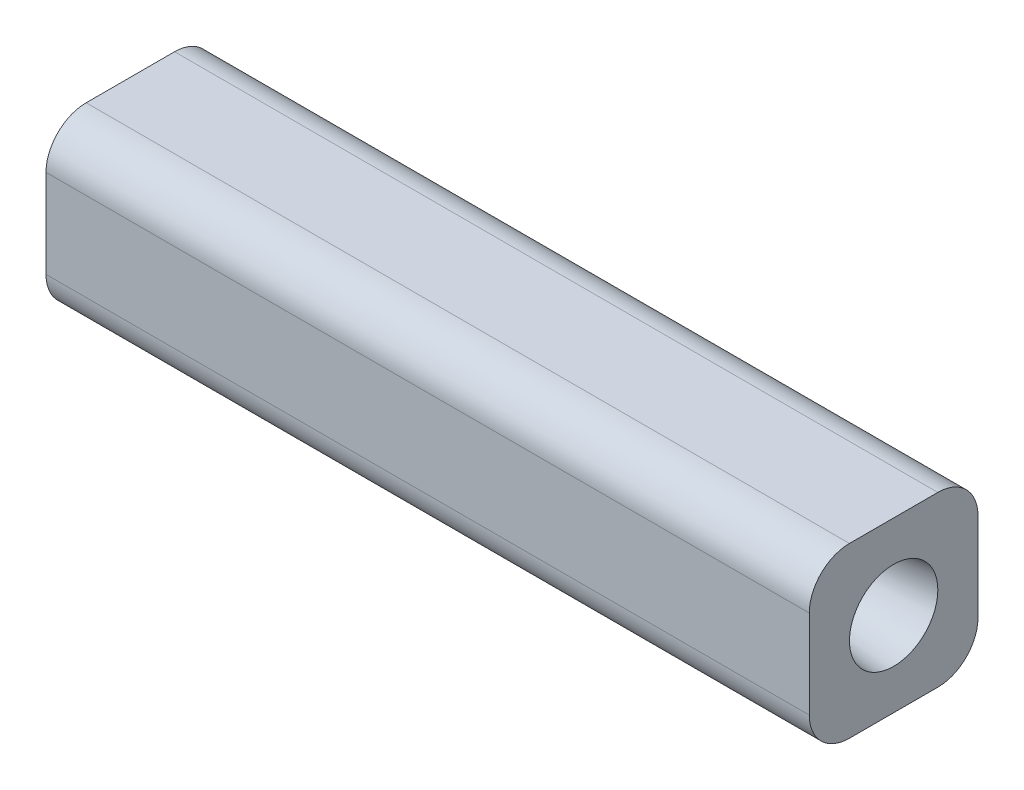
SolidWorks part; units mm, degrees
ref_plane "Front Plane" through (0, 0, 0) normal (1, 0, 0) x (0, 1, 0)
ref_plane "Top Plane" through (0, 0, 0) normal (0, 0, 1) x (0, 1, 0)
ref_plane "Right Plane" through (0, 0, 0) normal (0, 1, 0) x (-1, 0, 0)
sketch "Sketch1" plane through (0, 0, 0) normal (1, 0, 0) x (0, 1, 0)
  line L0 (2.1, 4.2) -> (2.1, 0) construction
  line L1 (1, 0) -> (3.2, 0)
  line L2 (0, 1) -> (0, 3.2)
  line L3 (1, 4.2) -> (3.2, 4.2)
  line L4 (4.2, 1) -> (4.2, 3.2)
  line L5 (3.2, 2.2404) -> (3.2, 0.2892) construction
  line L6 (0.3815, 3.2) -> (3.3385, 3.2) construction
  arc A0 (1, 0) -> (0, 1) centre (1, 1) cw
  arc A1 (3.2, 0) -> (4.2, 1) centre (3.2, 1) ccw
  arc A2 (3.2, 4.2) -> (4.2, 3.2) centre (3.2, 3.2) cw
  arc A3 (0, 3.2) -> (1, 4.2) centre (1, 3.2) cw
  circle A4 centre (2.1, 2.1) radius 1.1
  point P7 (0, 0)
  point P12 (4.2, 4.2)
  point P15 (0, 4.2)
  dimension "D2" = 1
  dimension "D3" = 2.2
  dimension "D1" = 1
  dimension "D4" = 1
extrude "Boss-Extrude1" add sketch "Sketch1" along normal blind 19 contours L4 A2 L3 A3 L2 A0 L1 A1
extrude "Cut-Extrude1" cut sketch "Sketch1<3>" along normal blind 5 draft 6 contours A4
sketch "Sketch1<3>" plane through (0, 0, 0) normal (1, 0, 0) x (0, 1, 0) same geometry as "Sketch1"
ref_plane "Plane1" through (9.5, 0, 0) normal (1, 0, 0) x (0, 0, -1)
mirror "Mirror1" about plane through (9.5, 0, 0) normal (1, 0, 0) of "Cut-Extrude1"
